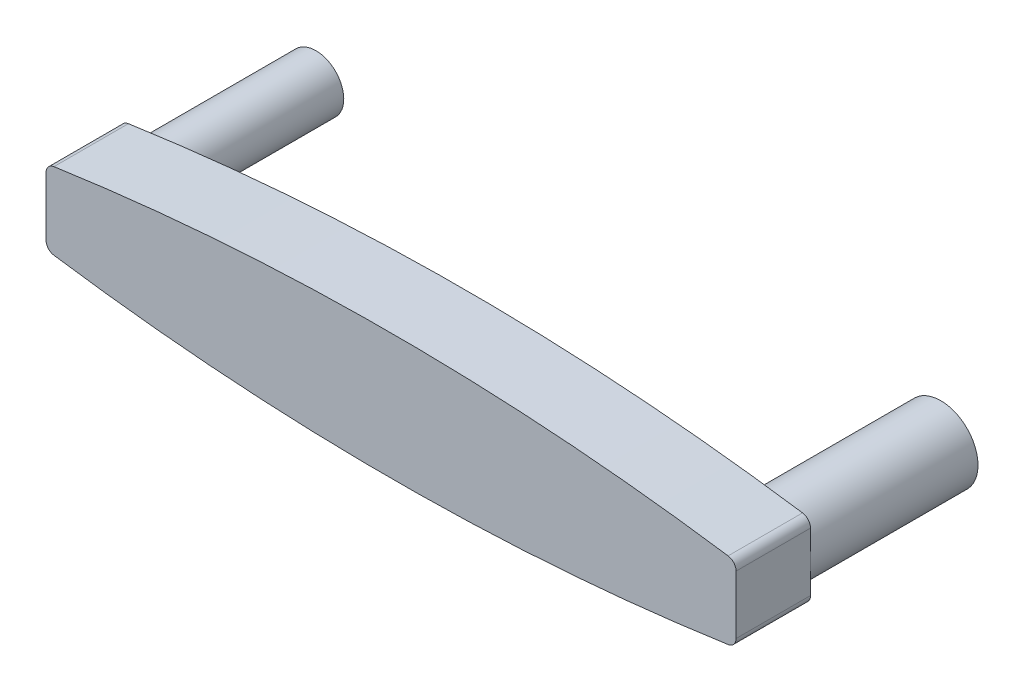
SolidWorks part; units mm, degrees
material "PLA 100% Infill"
ref_plane "Front Plane" through (0, 0, 0) normal (0, 0, 1) x (1, 0, 0)
ref_plane "Top Plane" through (0, 0, 0) normal (0, 1, 0) x (1, 0, 0)
ref_plane "Right Plane" through (0, 0, 0) normal (1, 0, 0) x (0, 0, -1)
sketch "Sketch1" plane through (0, 0, 0) normal (0, 0, 1) x (1, 0, 0)
  line L0 (0, -2) -> (37.08, -2) construction
  line L1 (0, 0) -> (37.08, 0) construction
  line L2 (0, 0) -> (0, -4)
  line L3 (0, -4) -> (37.08, -4) construction
  line L4 (37.08, 0) -> (37.08, -4)
  line L5 (36.2347, -2.6667) -> (33.9253, -2.6667)
  line L6 (33.9253, -2.6667) -> (35.08, -0.6667)
  line L7 (35.08, -0.6667) -> (36.2347, -2.6667)
  line L8 (35.08, -0.6667) -> (35.08, -2.6667) construction
  line L10 (35.6574, -1.6667) -> (33.9253, -2.6667) construction
  circle A0 centre (1.5, -2) radius 1.5
  circle A1 centre (35.08, -2) radius 2
  arc A3 (37.08, 0) -> (0, 0) centre (18.54, -123.6174) ccw
  arc A4 (37.08, -4) -> (0, -4) centre (18.54, 119.6174) cw
  point P18 (35.08, -2)
  point P19 (18.54, -21.2635)
  dimension "D2" = 3
  dimension "D3" = 4
  dimension "D5" = 2
  dimension "D6" = 250
  dimension "D1" = 4
  dimension "D4" = 33.58
extrude "Boss-Extrude1" add sketch "Sketch1" along normal blind 4 contours L4 A4 L2 A3
extrude "Boss-Extrude2" add sketch "Sketch1<3>" against normal blind 9 contours L0 A1 | A1 L0 | A0 L0 | L0 A0 | L5 L6 L7 region at (1.5, -2, 0) region at (33.1366, -2, 0)
sketch "Sketch1<3>" plane through (0, 0, 0) normal (0, 0, 1) x (1, 0, 0) same geometry as "Sketch1"
ref_plane "Plane1" [suppressed] through (0, 0, -19) normal (0, 0, -1) x (-1, 0, 0)
fillet "Fillet1" radius 0.5 4 edges at (37.08, -4, 2) (37.08, 0, 2) (0, -4, 2) (0, 0, 2)
